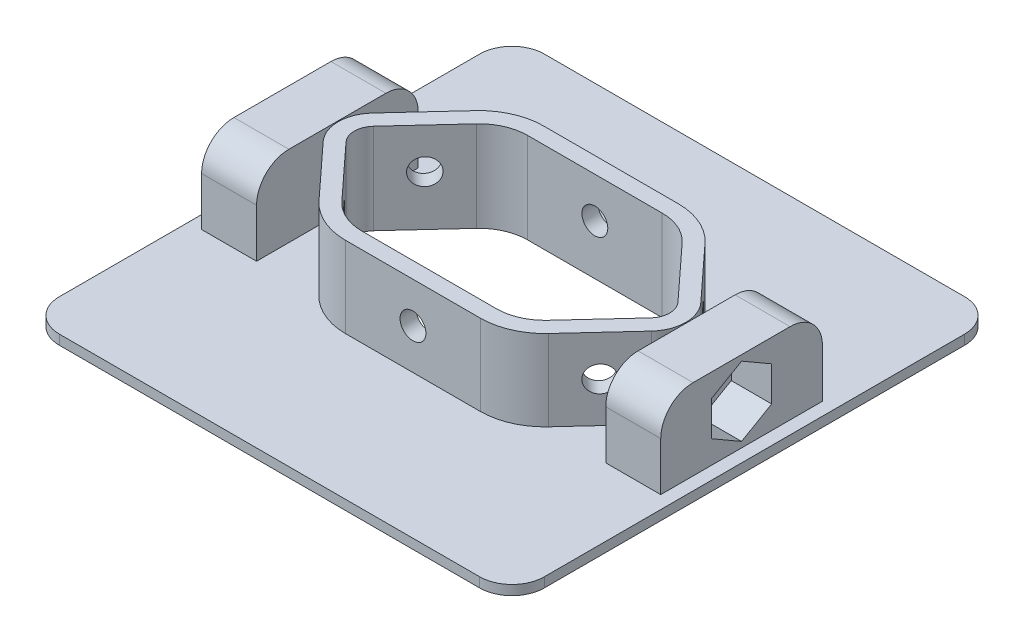
SolidWorks part; units mm, degrees
ref_plane "Front Plane" through (0, 0, 0) normal (0, 0, 1) x (1, 0, 0)
ref_plane "Top Plane" through (0, 0, 0) normal (0, 1, 0) x (1, 0, 0)
ref_plane "Right Plane" through (0, 0, 0) normal (1, 0, 0) x (0, 0, -1)
sketch "Sketch1" plane through (0, 0, 0) normal (0, 1, 0) x (1, 0, 0)
  line L1 (-30, -30) -> (30, -30)
  line L2 (-30, -30) -> (-30, 30)
  line L3 (-30, 30) -> (30, 30)
  line L4 (30, -30) -> (30, 30)
  line L5 (-30, -30) -> (30, 30) construction
  line L6 (-30, 30) -> (30, -30) construction
  point P0 (0, 0)
  dimension "D1" = 60
  dimension "D2" = 60
extrude "Boss-Extrude1" add sketch "Sketch1" along normal blind 1.2
fillet "Fillet1" radius 4 4 edges at (-30, 0.6, -30) (-30, 0.6, 30) (30, 0.6, -30) (30, 0.6, 30)
sketch "Sketch3" plane through (0, 1.2, 0) normal (0, 1, 0) x (1, 0, 0)
  line L4 (-28.4, -10) -> (-21.6, -10)
  line L5 (-28.4, -10) -> (-28.4, 10)
  line L6 (-28.4, 10) -> (-21.6, 10)
  line L7 (-21.6, -10) -> (-21.6, 10)
  line L8 (30, 0) -> (28.4, 0)
  line L9 (30, -26) -> (30, 26) construction
  line L11 (28.4, 10) -> (21.6, 10)
  line L12 (21.6, -10) -> (21.6, 10)
  line L13 (28.4, -10) -> (21.6, -10)
  line L14 (28.4, -10) -> (28.4, 10)
  dimension "D1" = 20
  dimension "D2" = 6.8
  dimension "D3" = 6.8
extrude "Boss-Extrude3" add sketch "Sketch3" along normal blind 10 contours L4 L7 L6 L5 | L13 L14 L11 L12 region at (-25, 1.2, 0) region at (25, 1.2, 0)
fillet "Fillet2" radius 4 4 edges at (25, 11.2, -10) (25, 11.2, 10) (-25, 11.2, 10) (-25, 11.2, -10)
sketch "Sketch4" plane through (-28.4, 0, 0) normal (-1, 0, 0) x (0, 0, 1)
  line L0 (0, 11.2) -> (0, 1.2)
  line L1 (6, 11.2) -> (-6, 11.2) construction
  line L2 (10, 1.2) -> (-10, 1.2) construction
  line L4 (0, 10.5) -> (-3.7239, 8.35)
  line L5 (-3.7239, 8.35) -> (-3.7239, 4.05)
  line L6 (-3.7239, 4.05) -> (0, 1.9)
  line L7 (0, 1.9) -> (3.7239, 4.05)
  line L8 (3.7239, 4.05) -> (3.7239, 8.35)
  line L9 (3.7239, 8.35) -> (0, 10.5)
  circle A0 centre (0, 6.2) radius 4.3 construction
  circle A1 centre (0, 6.2) radius 2
extrude "Cut-Extrude1" cut sketch "Sketch4" against normal blind 5 contours L5 L6 L0 L4 | L8 L9 L0 L7 region at (-28.4, 9.3438, 1.8151) region at (-28.4, 9.35, -0.0937)
sketch "Sketch5" plane through (0, 1.2, 0) normal (0, 1, 0) x (1, 0, 0)
  line L0 (18.8382, 1.6944) -> (12.7344, 8.3165)
  line L1 (8.3226, 10.25) -> (-8.3226, 10.25)
  line L2 (-12.7344, 8.3165) -> (-18.8382, 1.6944)
  line L3 (-12.7344, -8.3165) -> (-18.8382, -1.6944)
  line L4 (8.3226, -10.25) -> (-8.3226, -10.25)
  line L5 (18.8382, -1.6944) -> (12.7344, -8.3165)
  line L6 (20.3088, 3.0499) -> (14.205, 9.672)
  line L7 (8.3226, 12.25) -> (-8.3226, 12.25)
  line L8 (-14.205, 9.672) -> (-20.3088, 3.0499)
  line L9 (-14.205, -9.672) -> (-20.3088, -3.0499)
  line L10 (8.3226, -12.25) -> (-8.3226, -12.25)
  line L11 (20.3088, -3.0499) -> (14.205, -9.672)
  arc A0 (12.7344, 8.3165) -> (8.3226, 10.25) centre (8.3226, 4.25) ccw
  arc A1 (-8.3226, 10.25) -> (-12.7344, 8.3165) centre (-8.3226, 4.25) ccw
  arc A2 (-18.8382, 1.6944) -> (-18.8382, -1.6944) centre (-17, 0) ccw
  arc A3 (-8.3226, -10.25) -> (-12.7344, -8.3165) centre (-8.3226, -4.25) cw
  arc A4 (12.7344, -8.3165) -> (8.3226, -10.25) centre (8.3226, -4.25) cw
  arc A5 (18.8382, 1.6944) -> (18.8382, -1.6944) centre (17, 0) cw
  arc A6 (14.205, 9.672) -> (8.3226, 12.25) centre (8.3226, 4.25) ccw
  arc A7 (-8.3226, 12.25) -> (-14.205, 9.672) centre (-8.3226, 4.25) ccw
  arc A8 (-20.3088, 3.0499) -> (-20.3088, -3.0499) centre (-17, 0) ccw
  arc A9 (-8.3226, -12.25) -> (-14.205, -9.672) centre (-8.3226, -4.25) cw
  arc A10 (14.205, -9.672) -> (8.3226, -12.25) centre (8.3226, -4.25) cw
  arc A11 (20.3088, 3.0499) -> (20.3088, -3.0499) centre (17, 0) cw
extrude "Cut-Extrude2" cut sketch "Sketch5" against normal through all contours L1 A1 L2 A2 L3 A3 L4 A4 L5 A5 L0 A0
extrude "Boss-Extrude4" add sketch "Sketch5<3>" along normal blind 10
sketch "Sketch5<3>" plane through (0, 1.2, 0) normal (0, 1, 0) x (1, 0, 0) same geometry as "Sketch5"
sketch "Sketch6" plane through (0, 0, 12.25) normal (0, 0, 1) x (1, 0, 0)
  line L0 (0, 11.2) -> (0, 1.2) construction
  line L1 (-8.3226, 11.2) -> (8.3226, 11.2) construction
  line L2 (-8.3226, 1.2) -> (8.3226, 1.2) construction
  circle A0 centre (0, 6.2) radius 1.6
extrude "Cut-Extrude4" cut sketch "Sketch6" against normal up to surface (24.5 mm away) up to face at (0, 6.2, -12.25)
sketch "Sketch7" plane through (-12.5, 0, 11.5217) normal (-0.7353, 0, 0.6777) x (0.6777, 0, 0.7353)
  line L0 (-7.0187, 11.2) -> (-7.0187, 1.2) construction
  line L1 (-11.5217, 11.2) -> (-2.5156, 11.2) construction
  line L2 (-11.5217, 1.2) -> (-2.5156, 1.2) construction
  circle A0 centre (-7.0187, 6.2) radius 1.6
extrude "Cut-Extrude5" cut sketch "Sketch7" against normal up to next
sketch "Sketch8" plane through (12.5, 0, 11.5217) normal (0.7353, 0, 0.6777) x (0.6777, 0, -0.7353)
  line L0 (7.0187, 11.2) -> (7.0187, 1.2) construction
  line L1 (2.5156, 11.2) -> (11.5217, 11.2) construction
  line L2 (2.5156, 1.2) -> (11.5217, 1.2) construction
  circle A0 centre (7.0187, 6.2) radius 1.6
extrude "Cut-Extrude6" cut sketch "Sketch8" against normal up to next
sketch "Sketch9" plane through (-12.5, 0, -11.5217) normal (-0.7353, 0, -0.6777) x (-0.6777, 0, 0.7353)
  line L0 (7.0187, 11.2) -> (7.0187, 1.2) construction
  line L1 (2.5156, 11.2) -> (11.5217, 11.2) construction
  line L2 (2.5156, 1.2) -> (11.5217, 1.2) construction
  circle A0 centre (7.0187, 6.2) radius 1.6
extrude "Cut-Extrude7" cut sketch "Sketch9" against normal up to next
sketch "Sketch10" plane through (12.5, 0, -11.5217) normal (0.7353, 0, -0.6777) x (-0.6777, 0, -0.7353)
  line L0 (-7.0187, 11.2) -> (-7.0187, 1.2) construction
  line L1 (-11.5217, 11.2) -> (-2.5156, 11.2) construction
  line L2 (-11.5217, 1.2) -> (-2.5156, 1.2) construction
  circle A0 centre (-7.0187, 6.2) radius 1.6
extrude "Cut-Extrude8" cut sketch "Sketch10" against normal up to next
sketch "Sketch13" plane through (-28.4, 0, 0) normal (-1, 0, 0) x (0, 0, 1)
  circle A0 centre (0, 6.2) radius 2
extrude "Cut-Extrude10" cut sketch "Sketch13" against normal up to surface (6.8 mm away) up to face at (-21.6, 6.8095, 0)
sketch "Sketch14" plane through (28.4, 0, 0) normal (1, 0, 0) x (0, 0, -1)
  line L0 (0, 11.2) -> (0, 1.2)
  line L1 (0, 10.5) -> (-3.7239, 8.35)
  line L2 (-3.7239, 8.35) -> (-3.7239, 4.05)
  line L3 (-3.7239, 4.05) -> (0, 1.9)
  line L4 (0, 1.9) -> (3.7239, 4.05)
  line L5 (3.7239, 4.05) -> (3.7239, 8.35)
  line L6 (3.7239, 8.35) -> (0, 10.5)
  line L7 (-6, 11.2) -> (6, 11.2)
  line L8 (-6, 11.2) -> (6, 11.2) construction
  circle A0 centre (0, 6.2) radius 4.3 construction
  arc A1 (-6, 11.2) -> (-10, 7.2) centre (-6, 7.2) ccw construction
  circle A2 centre (0, 6.2) radius 2
extrude "Cut-Extrude11" cut sketch "Sketch14" against normal blind 5 contours A2 L0 L4 L5 L6 | A2 L0 L1 L2 L3 region at (28.4, 9.3438, -1.8151) region at (28.4, 9.35, 0.0937)
extrude "Cut-Extrude12" cut sketch "Sketch14<4>" against normal up to surface (6.8 mm away) contours L0 A2 | L0 A2 region at (28.4, 6.2, -0.8488) region at (28.4, 6.2, 0.8488) up to face at (21.6, 6.8095, 0)
sketch "Sketch14<4>" plane through (28.4, 0, 0) normal (1, 0, 0) x (0, 0, -1) same geometry as "Sketch14"
